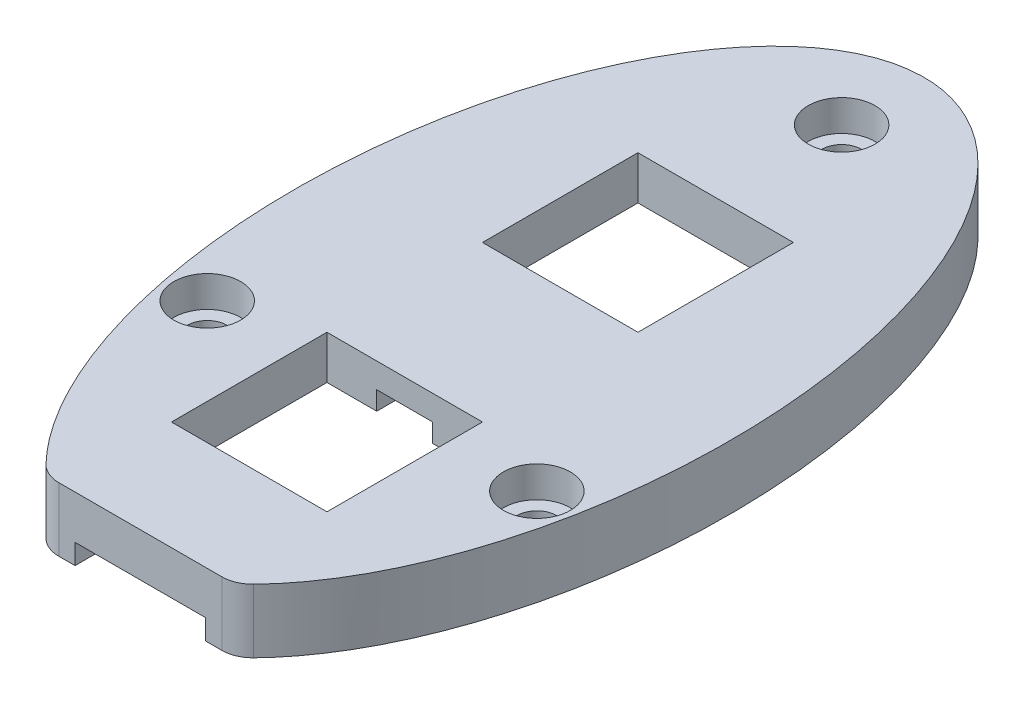
SolidWorks part; units mm, degrees
ref_plane "Front Plane" through (0, 0, 0) normal (0, 0, 1) x (1, 0, 0)
ref_plane "Top Plane" through (0, 0, 0) normal (0, 1, 0) x (1, 0, 0)
ref_plane "Right Plane" through (0, 0, 0) normal (1, 0, 0) x (0, 0, -1)
sketch "Sketch1" plane through (0, 0, 0) normal (0, 1, 0) x (1, 0, 0)
  line L0 (-7.6805, -30.353) -> (7.6805, -30.353)
  ellipse E0 centre (0, 0) end of major axis (0, -33.655) minor radius 17.78 (7.6805, -30.353) -> (-7.6805, -30.353) ccw
  dimension "D1" = 67.31
  dimension "D2" = 35.56
  dimension "D3" = 64.008
extrude "Boss-Extrude1" add sketch "Sketch1" against normal blind 2.032
sketch "Sketch17" plane through (0, 0, 0) normal (0, 1, 0) x (1, 0, 0)
  line L0 (0, 0) -> (0, 50.5429) construction
  line L1 (-6.35, 16.637) -> (6.35, 16.637)
  line L2 (-6.35, 16.637) -> (-6.35, 3.937)
  line L3 (-6.35, 3.937) -> (6.35, 3.937)
  line L4 (6.35, 16.637) -> (6.35, 3.937)
  line L5 (-6.35, 16.637) -> (6.35, 3.937) construction
  line L6 (-6.35, 3.937) -> (6.35, 16.637) construction
  line L7 (-6.35, -8.763) -> (6.35, -8.763)
  line L8 (-6.35, -8.763) -> (-6.35, -21.463)
  line L9 (-6.35, -21.463) -> (6.35, -21.463)
  line L10 (6.35, -8.763) -> (6.35, -21.463)
  line L11 (-6.35, -8.763) -> (6.35, -21.463) construction
  line L12 (-6.35, -21.463) -> (6.35, -8.763) construction
  line L13 (-7.6805, -30.353) -> (7.6805, -30.353) construction
  point P0 (0, 10.287)
  point P5 (0, -15.113)
  dimension "D1" = 12.7
  dimension "D2" = 15.24
  dimension "D3" = 40.64
extrude "Cut-Extrude13" cut sketch "Sketch17" against normal through all
sketch "Sketch18" plane through (0, -2.032, 0) normal (0, 1, 0) x (1, 0, 0)
  line L105 (-8.382, 18.669) -> (-8.382, 1.905)
  line L106 (-8.382, 1.905) -> (8.382, 1.905)
  line L107 (8.382, 1.905) -> (8.382, 18.669)
  line L108 (8.382, 18.669) -> (-8.382, 18.669)
  line L109 (-8.382, 18.669) -> (-8.382, 1.905)
  line L110 (-8.382, 1.905) -> (-2.286, 1.905)
  line L111 (8.382, 1.905) -> (8.382, 18.669)
  line L112 (8.382, 18.669) -> (-8.382, 18.669)
  line L113 (-6.35, 16.637) -> (-6.35, 3.937) construction
  line L114 (6.35, 16.637) -> (-6.35, 16.637) construction
  line L115 (-6.35, 3.937) -> (6.35, 3.937) construction
  line L116 (6.35, 3.937) -> (6.35, 16.637) construction
  line L117 (8.382, -23.495) -> (8.382, -6.731)
  line L118 (8.382, -6.731) -> (-8.382, -6.731)
  line L119 (-8.382, -6.731) -> (-8.382, -23.495)
  line L120 (-8.382, -23.495) -> (8.382, -23.495)
  line L121 (8.382, -23.495) -> (8.382, -6.731)
  line L122 (8.382, -6.731) -> (2.286, -6.731)
  line L123 (-8.382, -6.731) -> (-8.382, -23.495)
  line L124 (-8.382, -23.495) -> (8.382, -23.495)
  line L125 (-6.35, 16.637) -> (-6.35, 3.937)
  line L126 (6.35, 16.637) -> (-6.35, 16.637)
  line L127 (-6.35, 3.937) -> (-2.286, 3.937)
  line L128 (6.35, 3.937) -> (6.35, 16.637)
  line L129 (6.35, -8.763) -> (-6.35, -8.763) construction
  line L130 (6.35, -21.463) -> (6.35, -8.763) construction
  line L131 (-6.35, -21.463) -> (6.35, -21.463) construction
  line L132 (-6.35, -8.763) -> (-6.35, -21.463) construction
  line L133 (6.35, -8.763) -> (2.286, -8.763)
  line L134 (6.35, -21.463) -> (6.35, -8.763)
  line L135 (-6.35, -21.463) -> (6.35, -21.463)
  line L136 (-6.35, -8.763) -> (-6.35, -21.463)
  line L137 (-2.286, -8.763) -> (-2.286, -6.731)
  line L139 (2.286, 3.937) -> (2.286, 1.905)
  line L141 (0, 0) -> (0, 31.2149) construction
  line L142 (2.286, 1.905) -> (8.382, 1.905)
  line L143 (2.286, 3.937) -> (6.35, 3.937)
  line L144 (-2.286, -6.731) -> (-8.382, -6.731)
  line L145 (-2.286, -8.763) -> (-6.35, -8.763)
  line L146 (-2.286, 1.905) -> (-2.286, 3.937)
  line L147 (2.286, -6.731) -> (2.286, -8.763)
  dimension "D3" = 4.572
  dimension "D1" = 2.032
  dimension "D2" = 2.032
extrude "LightBox" add sketch "Sketch18" against normal blind 1.524
sketch "Sketch19" plane through (0, -2.032, 0) normal (0, -1, 0) x (1, 0, 0)
  line L0 (0, 0) -> (0, 18.966) construction
  circle A0 centre (-13.462, 11.43) radius 1.6256
  circle A1 centre (13.462, 11.43) radius 1.6256
  circle A2 centre (13.462, 11.43) radius 2.921
  circle A3 centre (-13.462, 11.43) radius 2.921
  circle A4 centre (0, -26.924) radius 1.6256
  circle A5 centre (0, -26.924) radius 2.921
  dimension "D3" = 3.2512
  dimension "D4" = 5.842
  dimension "D1" = 11.43
  dimension "D2" = 26.924
  dimension "D5" = 26.924
extrude "Boss-Screws" add sketch "Sketch19" along normal up to surface (1.524 mm away) up to face at (0, -3.556, 12.6577)
sketch "Sketch20" plane through (0, -2.032, 0) normal (0, -1, 0) x (1, 0, 0)
  line L0 (-7.6805, 30.353) -> (7.6805, 30.353) construction
  line L1 (-7.6805, 30.353) -> (7.6805, 30.353)
  line L2 (-6.8683, 28.321) -> (6.8683, 28.321)
  ellipse E0 centre (0, 0) end of major axis (0, 33.655) minor radius 17.78 (-7.6805, 30.353) -> (7.6805, 30.353) ccw construction
  ellipse E1 centre (0, 0) end of major axis (0, 33.655) minor radius 17.78 (-7.6805, 30.353) -> (7.6805, 30.353) ccw
  spline S0 degree 1 poles (-6.8683, 28.321) (6.8683, 28.321) knots 0 0 1 1 construction
  spline S1 degree 3 poles (-6.8683, 28.321) (-7.0654, 28.1239) (-7.4445, 27.7253) (-8.2052, 26.8467) (-9.126, 25.6276) (-10.1793, 23.9714) (-11.4956, 21.525) (-12.9504, 18.0525) (-14.3215, 13.3487) (-15.2684, 8.25) (-15.9229, 1.1274) (-15.5513, -7.99) (-13.2546, -17.9963) (-9.4231, -25.8847) (-5.4739, -29.882) (-2.314, -31.3833) (0, -31.7429) (2.314, -31.3833) (5.4739, -29.882) (9.4231, -25.8847) (13.2546, -17.9963) (15.5513, -7.99) (15.9229, 1.1274) (15.2684, 8.25) (14.3215, 13.3487) (12.9504, 18.0525) (11.4956, 21.525) (10.1793, 23.9714) (9.126, 25.6276) (8.2052, 26.8467) (7.4445, 27.7253) (7.0654, 28.1239) (6.8683, 28.321) knots 0.48601 0.48601 0.48601 0.48601 0.527503 0.568997 0.651984 0.73497 0.817957 0.983931 1.149905 1.315879 1.481853 1.813801 2.145749 2.477697 2.809645 2.975619 3.141593 3.307567 3.473541 3.805488 4.137436 4.469384 4.801332 4.967306 5.13328 5.299254 5.465228 5.548215 5.631202 5.714189 5.755682 5.797176 5.797176 5.797176 5.797176
  dimension "D1" = 2.032
extrude "FlangeOuter" add sketch "Sketch20" along normal blind 3.175
sketch "Sketch27" plane through (0, -3.556, 0) normal (0, -1, 0) x (1, 0, 0)
  circle A0 centre (-13.462, 11.43) radius 1.6256
  arc A1 (-14.3669, 12.7804) -> (-14.8218, 10.5393) centre (-13.462, 11.43) ccw construction
  circle A2 centre (13.462, 11.43) radius 1.6256
  arc A3 (14.3669, 12.7804) -> (14.8218, 10.5393) centre (13.462, 11.43) ccw construction
  circle A4 centre (0, -26.924) radius 1.6256 construction
  circle A5 centre (0, -26.924) radius 1.6256
extrude "Cut-Extrude16" cut sketch "Sketch27" against normal through all and the other way through all
sketch "Sketch28" plane through (0, 0, 0) normal (0, 1, 0) x (1, 0, 0)
  circle A0 centre (-13.462, -11.43) radius 2.7305
  circle A1 centre (13.462, -11.43) radius 2.7305
  circle A2 centre (0, 26.924) radius 2.7305
  dimension "D1" = 5.461
extrude "Cut-Extrude17" cut sketch "Sketch28" against normal blind 2.54
sketch "Sketch21" plane through (0, 0, 30.353) normal (0, 0, 1) x (1, 0, 0)
  line L0 (7.6805, -5.207) -> (-7.6805, -5.207) construction
  line L1 (-5.334, -5.207) -> (5.334, -5.207)
  line L2 (-5.334, -5.207) -> (-5.334, -3.556)
  line L3 (-5.334, -3.556) -> (5.334, -3.556)
  line L4 (5.334, -5.207) -> (5.334, -3.556)
  line L5 (0, 0) -> (0, -14.4473) construction
  line L6 (-7.6805, 0) -> (7.6805, 0) construction
  line L7 (-8.382, -3.556) -> (8.382, -3.556) construction
  dimension "D2" = 10.668
extrude "Cut-Extrude14" cut sketch "Sketch21" against normal up to next
sketch "Sketch22" plane through (0, 0, 0) normal (0, 1, 0) x (1, 0, 0)
  line L0 (0, 0) -> (0, 47.2593) construction
  line L1 (-25.4, 53.34) -> (25.4, 53.34)
  line L2 (-25.4, 53.34) -> (-25.4, 27.94)
  line L3 (-25.4, 27.94) -> (25.4, 27.94)
  line L4 (25.4, 53.34) -> (25.4, 27.94)
  dimension "D1" = 27.94
  dimension "D2" = 25.4
  dimension "D3" = 50.8
extrude "Cut-Extrude15" [suppressed] cut sketch "Sketch22" against normal offset from surface (1.524 mm away) 2.032 up to face at (12.9785, -3.556, 10.9328)
sketch "Sketch25" [suppressed] plane through (0, -1.524, 0) normal (0, 1, 0) x (1, 0, 0)
  line L0 (-9.2845, 28.702) -> (9.2845, 28.702)
  line L1 (-9.912, 27.94) -> (-2.5344, 27.94) construction
  ellipse E0 centre (0, 0) end of major axis (0, -33.655) minor radius 17.78 (9.912, 27.94) -> (-9.912, 27.94) ccw construction
  ellipse E1 centre (0, 0) end of major axis (0, -33.655) minor radius 17.78 (9.2845, 28.702) -> (-9.2845, 28.702) ccw
  dimension "D1" = 0.762
extrude "Boss-Extrude8" [suppressed] add sketch "Sketch25" against normal through all
fillet "Fillet1" radius 2.54 2 edges at (7.6805, -2.6035, 30.353) (-7.6805, -2.6035, 30.353)
